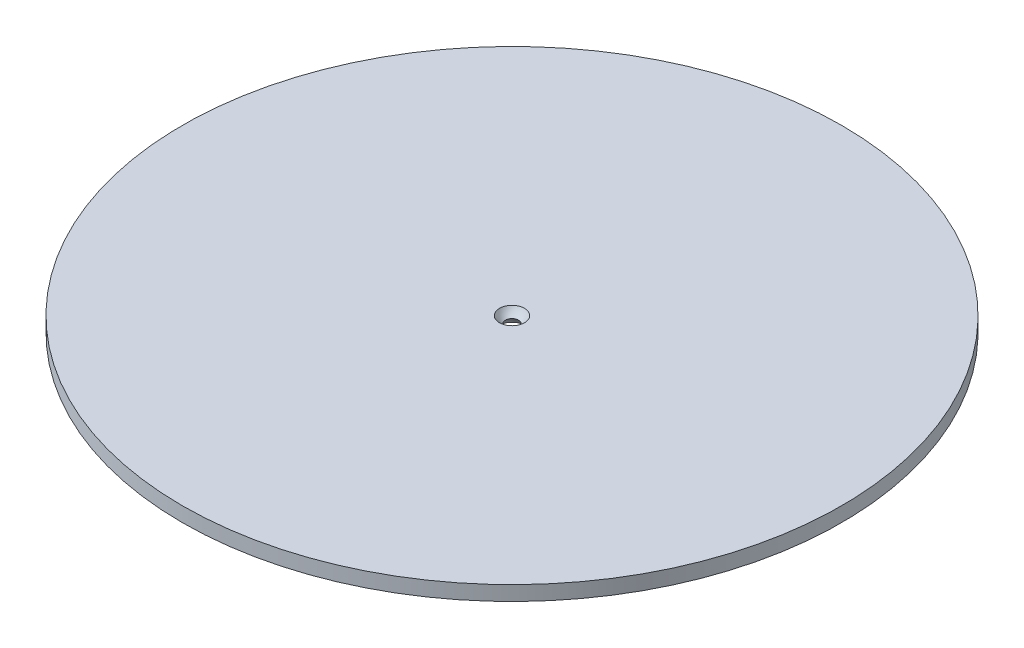
SolidWorks part; units mm, degrees
ref_plane "Front Plane" through (0, 0, 0) normal (0, 0, 1) x (1, 0, 0)
ref_plane "Top Plane" through (0, 0, 0) normal (0, 1, 0) x (1, 0, 0)
ref_plane "Right Plane" through (0, 0, 0) normal (1, 0, 0) x (0, 0, -1)
sketch "Sketch1" plane through (0, 0, 0) normal (0, 1, 0) x (1, 0, 0)
  circle A0 centre (0, 0) radius 1125
  dimension "D1" = 2250
extrude "Boss-Extrude1" add sketch "Sketch1" along normal blind 50
sketch "Sketch2" plane through (0, 0, 0) normal (0, 0, 1) x (1, 0, 0)
  line L0 (0, 0) -> (0, 50)
  line L1 (1125, 50) -> (-1125, 50) construction
  line L2 (0, 50) -> (42.7041, 50)
  line L3 (0, 0) -> (42.7041, 0)
  line L4 (-1125, 0) -> (1125, 0) construction
  arc A0 (42.7041, 0) -> (22.2813, 25.3377) centre (-15.9296, -26.3607) ccw
  arc A1 (22.2813, 25.3377) -> (42.7041, 50) centre (-18.8579, 80.1921) ccw
revolve "Cut-Revolve1" cut sketch "Sketch2" angle 360 about L0
